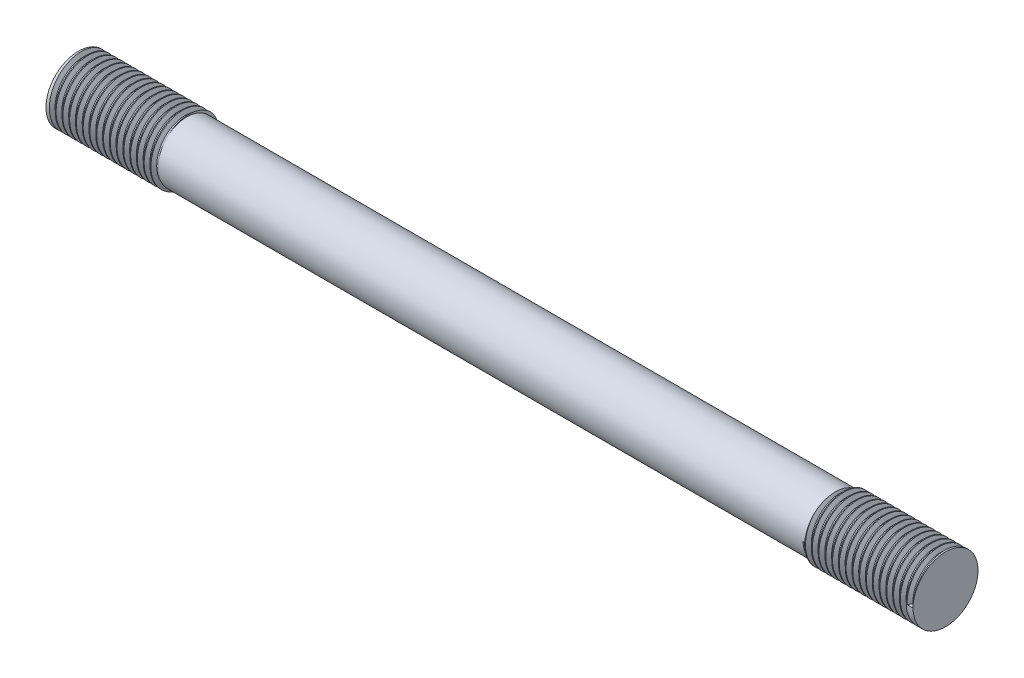
SolidWorks part; units mm, degrees
ref_plane "Front Plane" through (0, 0, 0) normal (1, 0, 0) x (0, 1, 0)
ref_plane "Top Plane" through (0, 0, 0) normal (0, 0, 1) x (0, 1, 0)
ref_plane "Right Plane" through (0, 0, 0) normal (0, 1, 0) x (-1, 0, 0)
sketch "Sketch1" plane through (0, 0, 0) normal (1, 0, 0) x (0, 1, 0)
  circle A0 centre (0, 0) radius 5.5
  dimension "D1" = 11
extrude "Boss-Extrude1" add sketch "Sketch1" along normal blind 160
sketch "Sketch2" plane through (160, 0, 0) normal (1, 0, 0) x (0, 1, 0)
  circle A0 centre (0, 0) radius 6
  dimension "D1" = 12
extrude "Boss-Extrude2" add sketch "Sketch2" against normal blind 20
sketch "Sketch3" plane through (0, 0, 0) normal (-1, 0, 0) x (0, -1, 0)
  circle A0 centre (0, 0) radius 6
extrude "Boss-Extrude3" add sketch "Sketch3" against normal blind 20
thread "Thread1" pitch 1.25 method cut profile "Thread Profile1" start angle 0, offset 0, length 0, pitch 1.25, diameter 12
ref_plane "Plane1" through (160, 0, 6) normal (0, -1, 0) x (0, 0, 1)
sketch "Thread Profile1" plane through (160, 0, 6) normal (0, -1, 0) x (0, 0, 1)
  line L0 (0, 0) -> (0, 1.25) construction
  line L11 (0, 0) -> (0, 1.0937)
  line L12 (0, 1.0937) -> (-0.6766, 0.7031)
  line L13 (-0.6766, 0.7031) -> (-0.6766, 0.3906)
  line L15 (-0.6766, 0.3906) -> (0, 0)
  line L17 (-0.6766, 0.5469) -> (0, 0.5469) construction
  point P2 (0, 0)
  dimension "Pitch" = 1.25
  dimension "Profile_Angle" = 60
  dimension "Profile_Land" = 0.3125
  dimension "Profile_Height" = 0.6766
thread "Thread2" pitch 1.25 method cut profile "Thread Profile2" start angle 0, offset 0, length 0, pitch 1.25, diameter 12
ref_plane "Plane2" through (0, 0, -6) normal (0, -1, 0) x (0, 0, -1)
sketch "Thread Profile2" plane through (0, 0, -6) normal (0, -1, 0) x (0, 0, -1)
  line L0 (0, 0) -> (0, 1.25) construction
  line L11 (0, 0) -> (0, 1.0937)
  line L12 (0, 1.0937) -> (-0.6766, 0.7031)
  line L13 (-0.6766, 0.7031) -> (-0.6766, 0.3906)
  line L15 (-0.6766, 0.3906) -> (0, 0)
  line L17 (-0.6766, 0.5469) -> (0, 0.5469) construction
  point P2 (0, 0)
  dimension "Pitch" = 1.25
  dimension "Profile_Angle" = 60
  dimension "Profile_Land" = 0.3125
  dimension "Profile_Height" = 0.6766
